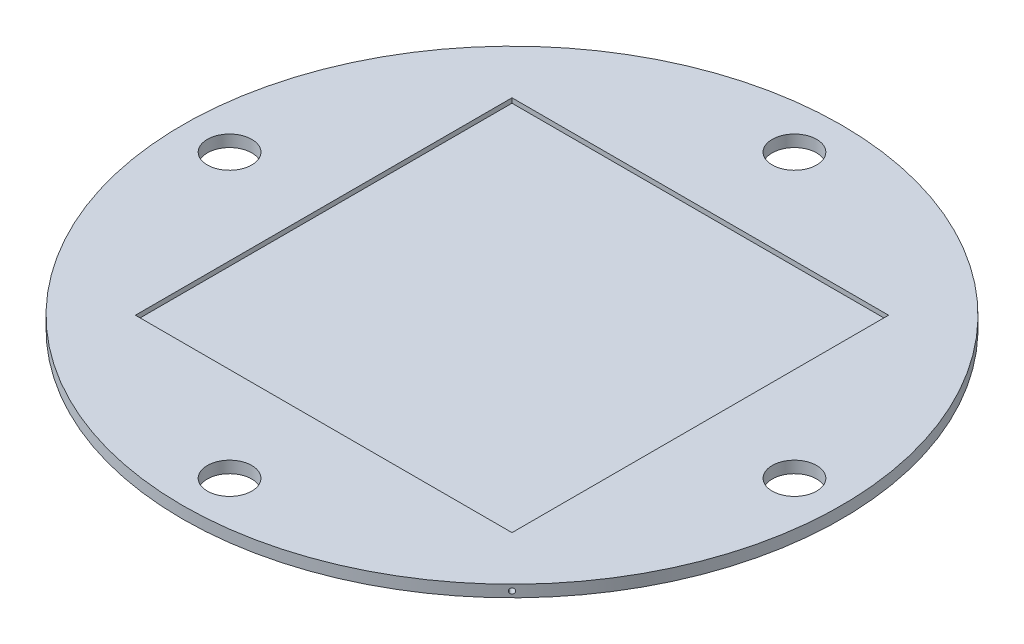
SolidWorks part; units mm, degrees
ref_plane "Front Plane" through (0, 0, 0) normal (0, 0, 1) x (1, 0, 0)
ref_plane "Top Plane" through (0, 0, 0) normal (0, 1, 0) x (1, 0, 0)
ref_plane "Right Plane" through (0, 0, 0) normal (1, 0, 0) x (0, 0, -1)
sketch "Sketch1" plane through (0, 0, 0) normal (0, 1, 0) x (1, 0, 0)
  circle A0 centre (0, 0) radius 88.9
  dimension "D1" = 177.8
extrude "Boss-Extrude1" add sketch "Sketch1" along normal blind 3.175
sketch "Sketch2" plane through (0, 3.175, 0) normal (0, 1, 0) x (1, 0, 0)
  circle A0 centre (0, 76.2) radius 5.9944
  dimension "D1" = 11.9888
  dimension "D2" = 76.2
extrude "Cut-Extrude1" cut sketch "Sketch2" against normal through all
pattern_circular "CirPattern1" count 4 over 360 about axis through (0, 3.175, 0) along (0, 1, 0) of "Cut-Extrude1"
ref_plane "Plane1" through (-62.8618, 0, 62.8618) normal (-0.7071, 0, 0.7071) x (0, -1, 0)
sketch "Sketch3" plane through (-62.8618, 0, 62.8618) normal (-0.7071, 0, 0.7071) x (0, -1, 0)
  line L0 (0, 0) -> (-3.1494, 0) construction
  circle A0 centre (-1.5875, 0) radius 0.6985
  dimension "D1" = 1.397
  dimension "D2" = 1.5875
extrude "Cut-Extrude2" cut sketch "Sketch3" against normal blind 3.175
pattern_circular "CirPattern2" count 4 over 360 about axis through (0, 3.175, 0) along (0, 1, 0) of "Cut-Extrude2"
sketch "Sketch4" plane through (0, 3.175, 0) normal (0, 1, 0) x (1, 0, 0)
  line L1 (-50.8, -50.8) -> (50.8, -50.8)
  line L2 (-50.8, -50.8) -> (-50.8, 50.8)
  line L3 (-50.8, 50.8) -> (50.8, 50.8)
  line L4 (50.8, -50.8) -> (50.8, 50.8)
  line L5 (-50.8, -50.8) -> (50.8, 50.8) construction
  line L6 (-50.8, 50.8) -> (50.8, -50.8) construction
  point P0 (0, 0)
  dimension "D1" = 101.6
  dimension "D2" = 101.6
extrude "Cut-Extrude3" cut sketch "Sketch4" against normal blind 1.27
